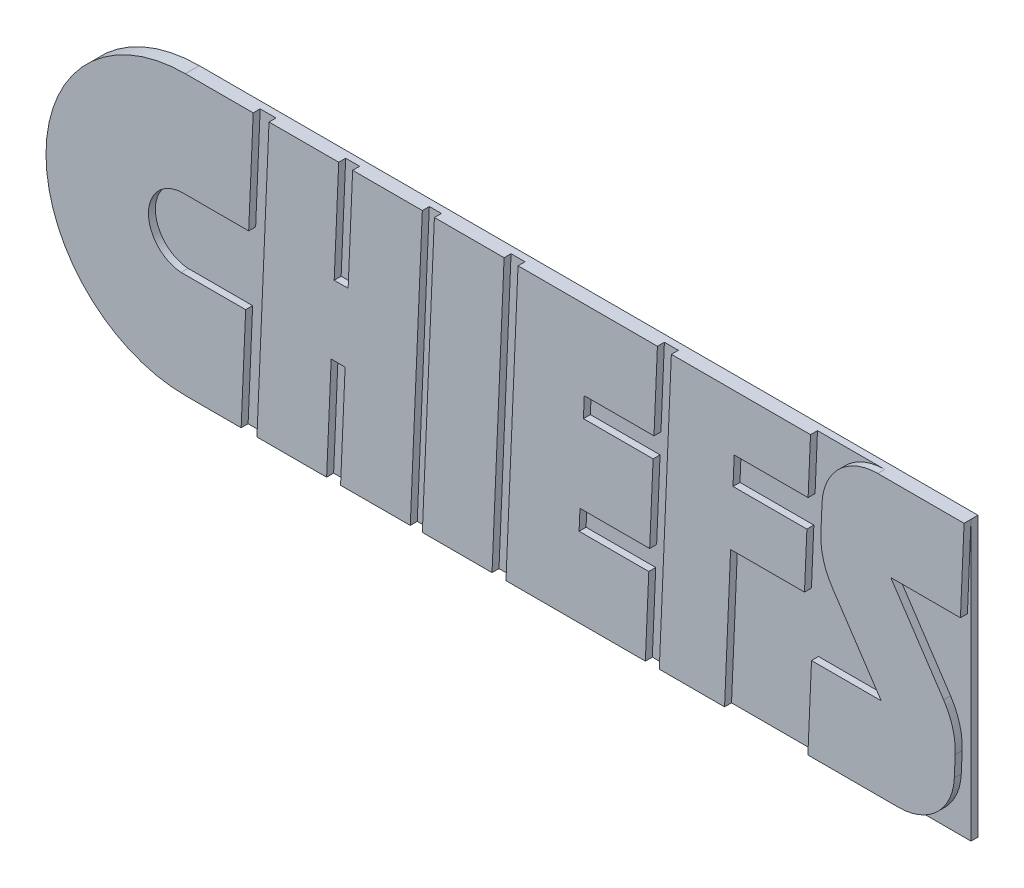
SolidWorks part; units mm, degrees
note: The reader was unsure of these and kept them because the rebuilt part matched: shared geometry of "Sketch5<4>".
ref_plane "Front Plane" through (0, 0, 0) normal (0, 0, 1) x (1, 0, 0)
ref_plane "Top Plane" through (0, 0, 0) normal (0, 1, 0) x (1, 0, 0)
ref_plane "Right Plane" through (0, 0, 0) normal (1, 0, 0) x (0, 0, -1)
sketch "Sketch2" plane through (0, 0, 0) normal (0, 0, 1) x (1, 0, 0)
  line L1 (25.4, 0) -> (167.2991, 0)
  line L3 (25.4, 50.8) -> (167.2991, 50.8)
  line L4 (167.2991, 0) -> (167.2991, 50.8)
  arc A0 (25.4, 50.8) -> (25.4, 0) centre (25.4, 25.4) ccw
  dimension "D1" = 25.4
  dimension "D2" = 141.8991
extrude "Extrude2" add sketch "Sketch2" along normal blind 1.27
sketch "Sketch5" plane through (0, 0, 1.27) normal (0, 0, 1) x (1, 0, 0)
  line L0 (25.4, 50.8) -> (37.7591, 50.8)
  line L1 (167.2991, 50.8) -> (25.4, 50.8) construction
  line L2 (25.4, 0) -> (35.56, 0)
  line L3 (36.9349, 31.7599) -> (37.7591, 50.8)
  line L4 (36.3849, 19.056) -> (35.56, 0)
  line L5 (36.3849, 19.056) -> (24.6247, 19.056)
  line L6 (36.9349, 31.7599) -> (25.1874, 31.7599)
  line L7 (166.639, 35.56) -> (153.939, 35.56)
  line L8 (40.64, 50.8) -> (38.4402, -0.0159)
  line L9 (38.4402, -0.0159) -> (51.1402, -0.0159)
  line L10 (51.1402, -0.0159) -> (51.9658, 19.056)
  line L11 (40.64, 50.8) -> (53.34, 50.8)
  line L12 (55.88, 50.8) -> (55.0558, 31.7599)
  line L13 (55.88, 50.8) -> (68.58, 50.8)
  line L14 (68.58, 50.8) -> (66.3808, -0.002)
  line L15 (152.2003, 15.24) -> (143.3192, 28.5946)
  line L16 (55.0558, 31.7599) -> (52.5158, 31.7599)
  line L17 (51.9658, 19.056) -> (54.5058, 19.056)
  line L18 (52.5158, 31.7599) -> (53.34, 50.8)
  line L19 (54.5058, 19.056) -> (53.6803, -0.0136)
  line L20 (68.58, 50.8) -> (70.7791, 50.8)
  line L21 (70.7791, 50.8) -> (68.58, 0)
  line L22 (68.58, 0) -> (81.28, 0)
  line L23 (81.28, 0) -> (83.4791, 50.8)
  line L24 (83.4791, 50.8) -> (70.7791, 50.8)
  line L25 (53.6803, -0.0136) -> (66.3808, -0.002)
  line L26 (86.0191, 50.8) -> (83.82, 0)
  line L27 (83.82, 0) -> (109.22, 0)
  line L28 (109.22, 0) -> (109.8462, 14.4645)
  line L29 (111.4191, 50.8) -> (86.0191, 50.8)
  line L30 (110.7931, 36.3388) -> (98.0931, 36.3388)
  line L31 (109.22, 0) -> (109.8462, 14.4645)
  line L32 (110.7931, 36.3388) -> (111.4191, 50.8)
  line L33 (110.6327, 32.6338) -> (97.9327, 32.6338)
  line L34 (110.0065, 18.1694) -> (110.6327, 32.6338)
  line L35 (110.0065, 18.1694) -> (97.3065, 18.1694)
  line L36 (97.3065, 18.1694) -> (97.1462, 14.4645)
  line L37 (97.1462, 14.4645) -> (109.8462, 14.4645)
  line L38 (98.0931, 36.3388) -> (97.9327, 32.6338)
  line L39 (139.5003, 15.24) -> (152.2003, 15.24)
  line L40 (113.9591, 50.8) -> (111.76, 0)
  line L41 (111.76, 0) -> (123.654, 0)
  line L42 (123.654, 0) -> (124.7536, 25.4)
  line L43 (113.9591, 50.8) -> (139.3183, 50.8)
  line L44 (139.3183, 50.8) -> (138.8784, 40.6376)
  line L45 (138.2188, 25.4) -> (124.7536, 25.4)
  line L46 (125.1935, 35.5624) -> (125.4132, 40.6376)
  line L47 (138.8784, 40.6376) -> (125.4132, 40.6376)
  line L48 (139.5003, 15.24) -> (138.8403, 0)
  line L49 (138.6587, 35.5624) -> (138.2188, 25.4)
  line L50 (138.6587, 35.5624) -> (125.1935, 35.5624)
  line L51 (151.5689, 50.8) -> (167.2991, 50.8)
  line L52 (141.4184, 41.0794) -> (141.2062, 36.1765)
  line L53 (167.2991, 50.8) -> (166.639, 35.56)
  line L54 (138.8403, 0) -> (155.3694, 0)
  line L55 (153.939, 35.56) -> (163.5703, 21.0773)
  line L56 (165.6834, 13.4951) -> (165.5199, 9.7204)
  arc A0 (25.1874, 31.7599) -> (24.6247, 19.056) centre (25.0275, 25.4026) ccw
  arc A1 (25.4, 50.8) -> (25.4, 0) centre (25.4, 25.4) ccw construction
  arc A2 (141.2062, 36.1765) -> (143.3192, 28.5946) centre (153.8943, 35.6273) ccw
  arc A3 (141.4184, 41.0794) -> (151.5689, 50.8) centre (151.5689, 40.64) cw
  arc A4 (165.5199, 9.7204) -> (155.3694, 0) centre (155.3694, 10.16) cw
  arc A5 (165.6834, 13.4951) -> (163.5703, 21.0773) centre (152.9953, 14.0447) ccw
  arc A6 (25.4, 50.8) -> (25.4, 0) centre (25.4, 25.4) ccw
  point P69 (141.8392, 50.8)
  point P74 (165.8625, 17.6306)
  point P75 (0, 25.4)
  point P76 (141.8392, 50.8)
  dimension "D1" = 15.24
  dimension "D2" = 167.2991
  dimension "D3" = 15.24
  dimension "D4" = 15.1862
  dimension "D5" = 12.7
  dimension "D6" = 12.7
  dimension "D7" = 12.7
  dimension "D8" = 2.54
  dimension "D9" = 92.479
  dimension "D10" = 87.52
  dimension "D11" = 87.52
extrude "Extrude3" add sketch "Sketch5" along normal blind 1.27 contours L6 A0 L5 L4 L2 A6 L0 L3
extrude "Extrude4" add sketch "Sketch5<4>" along normal blind 1.27
sketch "Sketch5<4>" plane through (0, 0, 1.27) normal (0, 0, 1) x (1, 0, 0) same geometry as "Sketch5"
